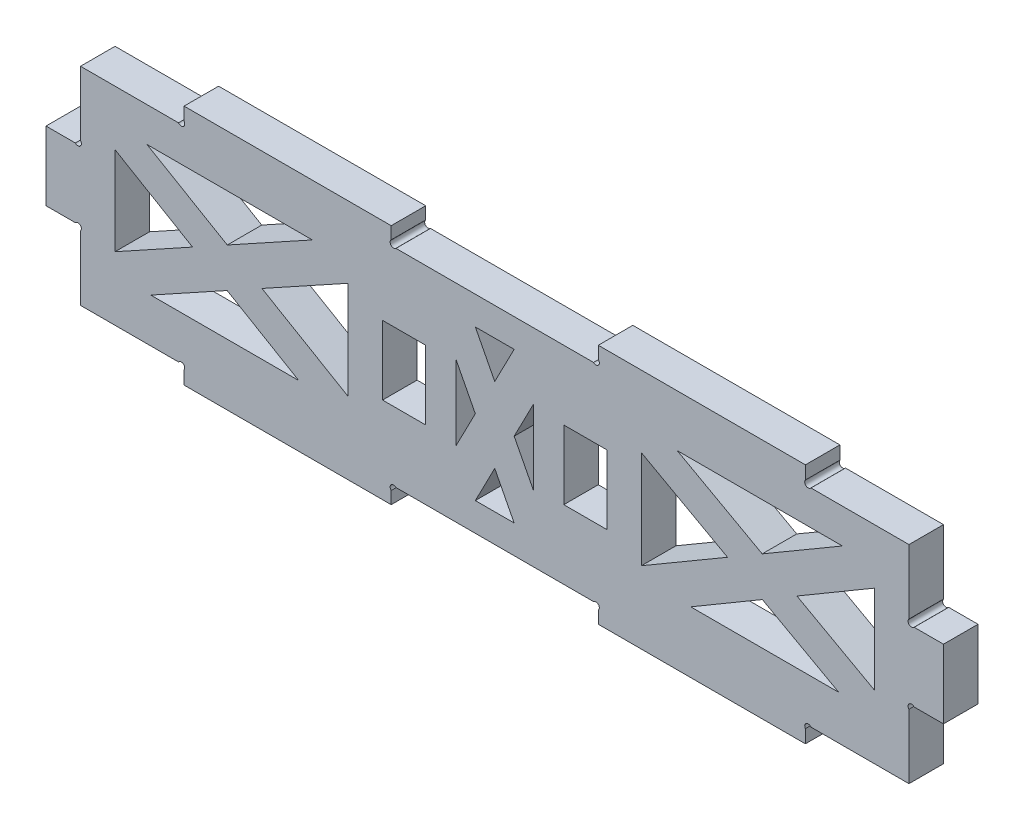
SolidWorks part; units mm, degrees
material "7050-T73510"
ref_plane "Front Plane" through (0, 0, 0) normal (0, 0, 1) x (1, 0, 0)
ref_plane "Top Plane" through (0, 0, 0) normal (0, 1, 0) x (1, 0, 0)
ref_plane "Right Plane" through (0, 0, 0) normal (1, 0, 0) x (0, 0, -1)
sketch "Sketch1" plane through (0, 0, 0) normal (0, 0, 1) x (1, 0, 0)
  line L1 (-165.1, -38.1) -> (165.1, -38.1)
  line L2 (-165.1, -38.1) -> (-165.1, 38.1)
  line L3 (-165.1, 38.1) -> (165.1, 38.1)
  line L4 (165.1, -38.1) -> (165.1, 38.1)
  line L5 (-165.1, -38.1) -> (165.1, 38.1) construction
  line L6 (-165.1, 38.1) -> (165.1, -38.1) construction
  point P0 (0, 0)
  dimension "D1" = 330.2
  dimension "D2" = 76.2
extrude "Boss-Extrude1" add sketch "Sketch1" along normal blind 12.7 contours L1 L3 region at (0, 0, 0)
sketch "Sketch2" plane through (0, 0, 12.7) normal (0, 0, 1) x (1, 0, 0)
  line L0 (-165.1, -38.1) -> (165.1, -38.1) construction
  line L1 (-38.1, -38.1) -> (-114.3, -38.1)
  line L2 (-38.1, -38.1) -> (-38.1, -44.45)
  line L3 (-38.1, -44.45) -> (-114.3, -44.45)
  line L4 (-114.3, -38.1) -> (-114.3, -44.45)
  line L5 (0, -6.985) -> (0, 6.985) construction
  line L6 (38.1, -44.45) -> (114.3, -44.45)
  line L7 (114.3, -38.1) -> (114.3, -44.45)
  line L8 (38.1, -38.1) -> (114.3, -38.1)
  line L9 (38.1, -38.1) -> (38.1, -44.45)
  line L10 (6.985, 0) -> (-6.985, 0) construction
  line L11 (38.1, 38.1) -> (38.1, 44.45)
  line L12 (38.1, 38.1) -> (114.3, 38.1)
  line L13 (114.3, 38.1) -> (114.3, 44.45)
  line L14 (38.1, 44.45) -> (114.3, 44.45)
  line L15 (-38.1, 44.45) -> (-114.3, 44.45)
  line L16 (-114.3, 38.1) -> (-114.3, 44.45)
  line L17 (-38.1, 38.1) -> (-114.3, 38.1)
  line L18 (-38.1, 38.1) -> (-38.1, 44.45)
  point P12 (-38.1, -41.275)
  dimension "D1" = 76.2
  dimension "D2" = 6.35
  dimension "D3" = 76.2
extrude "Boss-Extrude2" add sketch "Sketch2" against normal blind 12.7
sketch "Sketch3" plane through (0, 0, 12.7) normal (0, 0, 1) x (1, 0, 0)
  line L0 (6.985, 0) -> (-6.985, 0) construction
  line L1 (-165.1, -38.1) -> (-152.4, -38.1)
  line L2 (-165.1, -38.1) -> (-165.1, -12.7)
  line L3 (-165.1, -12.7) -> (-152.4, -12.7)
  line L4 (-152.4, -38.1) -> (-152.4, -12.7)
  line L6 (-165.1, 12.7) -> (-152.4, 12.7)
  line L7 (-152.4, 38.1) -> (-152.4, 12.7)
  line L8 (-165.1, 38.1) -> (-152.4, 38.1)
  line L9 (-165.1, 38.1) -> (-165.1, 12.7)
  line L10 (0, -6.985) -> (0, 6.985) construction
  line L11 (165.1, 38.1) -> (165.1, 12.7)
  line L12 (165.1, 38.1) -> (152.4, 38.1)
  line L13 (152.4, 38.1) -> (152.4, 12.7)
  line L14 (165.1, 12.7) -> (152.4, 12.7)
  line L15 (165.1, -12.7) -> (152.4, -12.7)
  line L16 (152.4, -38.1) -> (152.4, -12.7)
  line L17 (165.1, -38.1) -> (152.4, -38.1)
  line L18 (165.1, -38.1) -> (165.1, -12.7)
  line L19 (25.4, 12.7) -> (41.275, 12.7)
  line L20 (25.4, 12.7) -> (25.4, -12.7)
  line L21 (25.4, -12.7) -> (41.275, -12.7)
  line L22 (41.275, 12.7) -> (41.275, -12.7)
  line L23 (-38.1, -38.1) -> (38.1, -38.1) construction
  line L24 (-25.4, -12.7) -> (-41.275, -12.7)
  line L25 (-41.275, 12.7) -> (-41.275, -12.7)
  line L26 (-25.4, 12.7) -> (-41.275, 12.7)
  line L27 (-25.4, 12.7) -> (-25.4, -12.7)
  line L28 (-38.1, 38.1) -> (38.1, 38.1) construction
  dimension "D1" = 25.4
  dimension "D2" = 12.7
  dimension "D3" = 50.8
  dimension "D4" = 15.875
  dimension "D5" = 25.4
  dimension "D6" = 25.4
extrude "Cut-Extrude1" cut sketch "Sketch3" against normal through all
sketch "Sketch4" plane through (0, 0, 12.7) normal (0, 0, 1) x (1, 0, 0)
  line L0 (6.985, 0) -> (-6.985, 0) construction
  line L1 (-139.7, -21.8966) -> (-53.975, -21.8966)
  line L2 (-139.7, -21.8966) -> (-139.7, 25.4)
  line L3 (-139.7, 25.4) -> (-53.975, 25.4)
  line L4 (-53.975, -21.8966) -> (-53.975, 25.4)
  line L5 (-139.7, -21.8966) -> (-104.8218, -2.6534) construction
  line L6 (0, -6.985) -> (0, 6.985) construction
  line L7 (-152.4, 12.7) -> (-152.4, 38.1) construction
  line L8 (-41.275, 12.7) -> (-41.275, -12.7) construction
  line L9 (-152.4, 38.1) -> (-114.3, 38.1) construction
  line L10 (-139.7, 17.8609) -> (-111.1841, 1.0887)
  line L11 (-126.5551, -21.8966) -> (-98.4595, -6.3955)
  line L12 (-127.9201, 25.4) -> (-98.411, 8.136)
  line L13 (-139.7, -14.6442) -> (-111.1841, 1.0887)
  line L14 (-136.6325, -27.4565) -> (-50.9075, 19.8401) construction
  line L15 (-142.7675, -16.3366) -> (-57.0425, 30.9599) construction
  line L16 (100.0125, 0) -> (93.9026, 3.371) construction
  line L17 (139.7, -21.8966) -> (104.8218, -2.6534) construction
  line L18 (-98.411, 8.136) -> (-67.1199, 25.4)
  line L19 (85.6513, 0.6711) -> (53.975, -17.8609)
  line L20 (-100.0125, 0) -> (-93.9026, 3.371) construction
  line L21 (-139.7, -21.8966) -> (-53.975, 25.4) construction
  line L22 (-85.6513, 0.6711) -> (-53.975, 18.1476)
  line L23 (-98.4595, -6.3955) -> (-72.1049, -21.8966)
  line L24 (-85.6513, 0.6711) -> (-53.975, -17.8609)
  line L25 (98.4595, -6.3955) -> (72.1049, -21.8966)
  line L26 (85.6513, 0.6711) -> (53.975, 18.1476)
  line L27 (98.411, 8.136) -> (67.1199, 25.4)
  line L28 (139.7, -14.6442) -> (111.1841, 1.0887)
  line L29 (127.9201, 25.4) -> (98.411, 8.136)
  line L30 (126.5551, -21.8966) -> (98.4595, -6.3955)
  line L31 (139.7, 17.8609) -> (111.1841, 1.0887)
  line L32 (53.975, -21.8966) -> (53.975, 25.4)
  line L33 (139.7, 25.4) -> (53.975, 25.4)
  line L34 (139.7, -21.8966) -> (139.7, 25.4)
  line L35 (139.7, -21.8966) -> (53.975, -21.8966)
  line L41 (-14.2875, 13.8265) -> (7.1407, -27.665)
  line L42 (-14.2875, -27.665) -> (14.2875, -27.665)
  line L44 (-14.2875, -27.665) -> (-14.2875, 27.665)
  line L45 (-14.2875, 27.665) -> (14.2875, 27.665)
  line L46 (14.2875, -27.665) -> (14.2875, 27.665)
  line L47 (-14.2875, -27.665) -> (14.2875, 27.665) construction
  line L48 (-14.2875, 27.665) -> (14.2875, -27.665) construction
  line L49 (-7.1407, -27.665) -> (14.2875, 13.8265)
  line L50 (-7.1407, 27.665) -> (14.2875, -13.8265)
  line L51 (-14.2875, -13.8265) -> (7.1407, 27.665)
  line L52 (-8.6455, -30.5788) -> (19.9295, 24.7512) construction
  line L53 (-19.9295, -24.7512) -> (8.6455, 30.5788) construction
  line L54 (-19.9295, 24.7512) -> (8.6455, -30.5788) construction
  line L55 (-8.6455, 30.5788) -> (19.9295, -24.7512) construction
  point P0 (-100.0125, 0)
  point P53 (100.0125, 0)
  point P54 (0, 0)
  dimension "D1" = 12.7
  dimension "D2" = 12.7
  dimension "D3" = 12.7
  dimension "D6" = 28.575
  dimension "D7" = 6.35
  dimension "D4" = 6.35
  dimension "D5" = 6.35
  dimension "D8" = 6.35
extrude "Cut-Extrude2" cut sketch "Sketch4" against normal through all contours L22 L24 L4 | L2 L13 L10 | L12 L18 L3 | L23 L11 L1 | L32 L19 L26 | L35 L30 L25 | L29 L33 L27 | L28 L34 L31 | L45 | L44 | L46 | L42 region at (-99.0398, -16.7295, 12.7) region at (-130.1947, 1.4351, 12.7) region at (-64.5338, 0.3193, 12.7) region at (-97.817, 19.6453, 12.7) region at (64.5338, 0.3193, 12.7) region at (99.0398, -16.7295, 12.7) region at (97.817, 19.6453, 12.7) region at (130.1947, 1.4351, 12.7) region at (-11.9073, 0, 12.7) region at (0, -23.0561, 12.7) region at (0, 23.0561, 12.7) region at (11.9073, 0, 12.7)
sketch "Sketch7" plane through (0, 0, 12.7) normal (0, 0, 1) x (1, 0, 0)
  line L0 (0, -6.985) -> (0, 6.985) construction
  line L1 (6.985, 0) -> (-6.985, 0) construction
  circle A0 centre (-153.3572, -13.5347) radius 1.27
  circle A1 centre (-115.3222, -38.8536) radius 1.27
  circle A2 centre (-37.2199, -39.0156) radius 1.27
  circle A3 centre (37.2199, -39.0156) radius 1.27
  circle A4 centre (115.3222, -38.8536) radius 1.27
  circle A5 centre (153.3572, -13.5347) radius 1.27
  circle A6 centre (153.3572, 13.5347) radius 1.27
  circle A7 centre (115.3222, 38.8536) radius 1.27
  circle A8 centre (37.2199, 39.0156) radius 1.27
  circle A9 centre (-37.2199, 39.0156) radius 1.27
  circle A10 centre (-115.3222, 38.8536) radius 1.27
  circle A11 centre (-153.3572, 13.5347) radius 1.27
extrude "Cut-Extrude4" cut sketch "Sketch7" against normal through all
